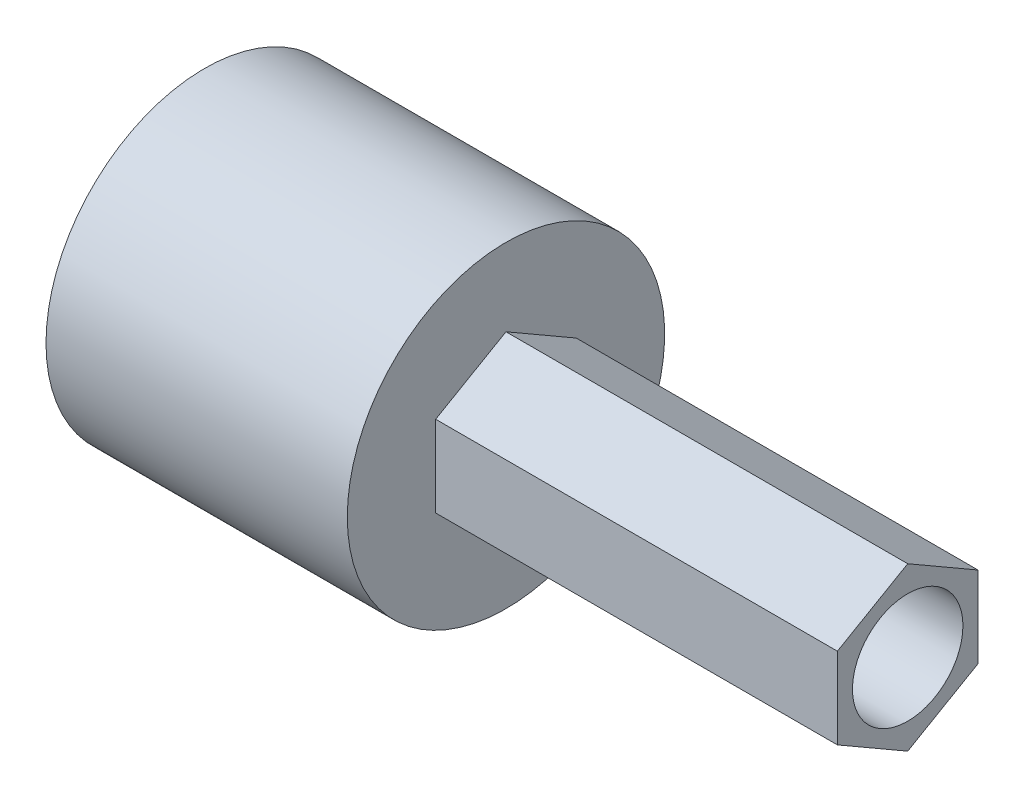
SolidWorks part; units mm, degrees
ref_plane "Alzado" through (0, 0, 0) normal (0, 0, 1) x (1, 0, 0)
ref_plane "Planta" through (0, 0, 0) normal (0, 1, 0) x (1, 0, 0)
ref_plane "Vista lateral" through (0, 0, 0) normal (1, 0, 0) x (0, 0, -1)
sketch "Croquis1" plane through (0, 0, 0) normal (1, 0, 0) x (0, 0, -1)
  line L0 (0, 0) -> (0, 4.0415) construction
  line L1 (-3.5, -2.0207) -> (0, -4.0415)
  line L2 (0, -4.0415) -> (3.5, -2.0207)
  line L3 (3.5, -2.0207) -> (3.5, 2.0207)
  line L4 (3.5, 2.0207) -> (0, 4.0415)
  line L5 (0, 4.0415) -> (-3.5, 2.0207)
  line L6 (-3.5, 2.0207) -> (-3.5, -2.0207)
  circle A0 centre (0, 0) radius 4.0415 construction
  circle A1 centre (0, 0) radius 3.5 construction
  dimension "D1" = 7
extrude "Saliente-Extruir1" add sketch "Croquis1" along normal blind 20
sketch "Croquis2" plane through (0, 0, 0) normal (-1, 0, 0) x (0, 0, 1)
  circle A0 centre (0, 0) radius 4.9
  circle A1 centre (0, 0) radius 7.9
  line M3 (3.5, -2.0207) -> (3.5, 2.0207)
  line M4 (3.5, 2.0207) -> (0, 4.0415)
  line M5 (0, 4.0415) -> (-3.5, 2.0207)
  line M6 (-3.5, 2.0207) -> (-3.5, -2.0207)
  line M7 (-3.5, -2.0207) -> (0, -4.0415)
  line M8 (0, -4.0415) -> (3.5, -2.0207)
  dimension "D1" = 3
  dimension "D2" = 9.8
extrude "Saliente-Extruir2" add sketch "Croquis2" along normal blind 3 contours A0 M3 M8 M7 M6 M5 M4 | A1 A0 | M8 M3 M4 M5 M6 M7 region at (0, 0, -4.7614) region at (0, 0, -7.6766) region at (0, 0, 0)
extrude "Saliente-Extruir3" add sketch "Croquis2<3>" along normal blind 12 from surface starting at face at (-3, 0, 7.9)
sketch "Croquis2<3>" plane through (0, 0, 0) normal (-1, 0, 0) x (0, 0, 1) same geometry as "Croquis2"
sketch "Croquis3" plane through (20, 0, 0) normal (1, 0, 0) x (0, 0, -1)
  circle A0 centre (0, 0) radius 2.75
  dimension "D1" = 5.5
extrude "Cortar-Extruir1" cut sketch "Croquis3" against normal through all
ref_plane "Plano1" through (17, 0, 0) normal (1, 0, 0) x (0, 0, -1)
sketch "Croquis4" plane through (-3, 0, 0) normal (-1, 0, 0) x (0, 0, 1)
  line L1 (3.5, -2.0207) -> (3.5, 2.0207)
  line L2 (3.5, 2.0207) -> (0, 4.0415)
  line L3 (0, 4.0415) -> (-3.5, 2.0207)
  line L4 (-3.5, 2.0207) -> (-3.5, -2.0207)
  line L5 (-3.5, -2.0207) -> (0, -4.0415)
  line L6 (0, -4.0415) -> (3.5, -2.0207)
  line L8 (0, 4.0415) -> (3.5, 2.0207) construction
  circle A0 centre (0, 0) radius 3.5 construction
  dimension "D1" = 7
sketch "Croquis5" plane through (-3, 0, 0) normal (-1, 0, 0) x (0, 0, 1)
  circle A0 centre (0, 0) radius 2.75
  circle A1 centre (0, 0) radius 2.75 construction
extrude "Saliente-Extruir4" add sketch "Croquis5" against normal blind 0.3
